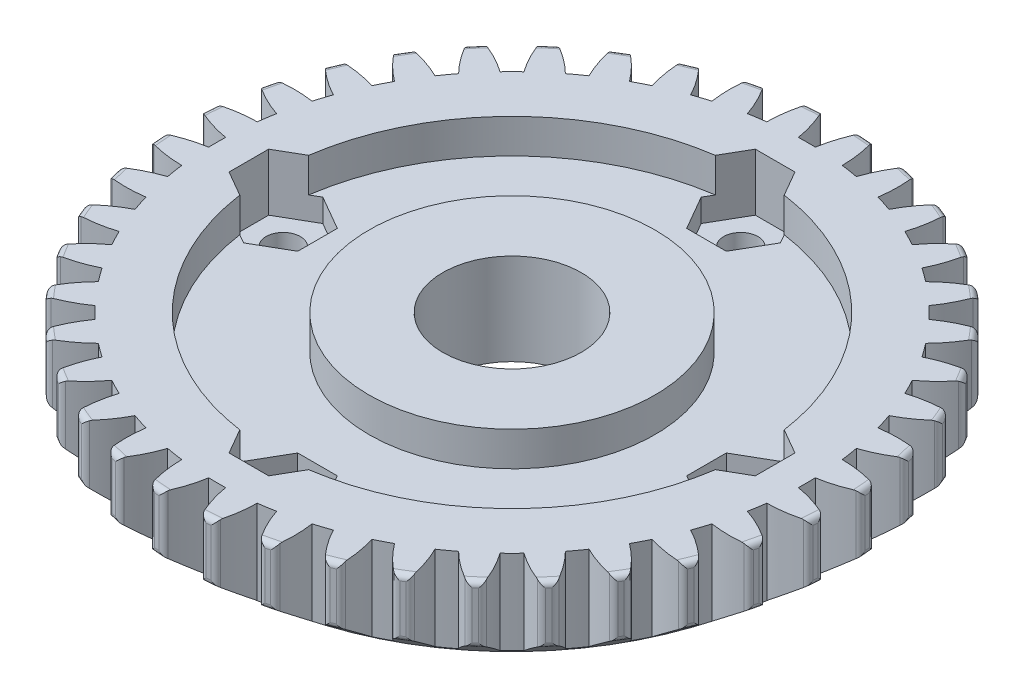
SolidWorks part; units mm, degrees
material "尼龙 101"
ref_plane "前视基准面" through (0, 0, 0) normal (0, 0, 1) x (1, 0, 0)
ref_plane "上视基准面" through (0, 0, 0) normal (0, 1, 0) x (1, 0, 0)
ref_plane "右视基准面" through (0, 0, 0) normal (1, 0, 0) x (0, 0, -1)
sketch "草图2" plane through (0, 0, 0) normal (0, 1, 0) x (1, 0, 0)
  line L0 (0, -1060.6686) -> (0, -25.7803) construction
  line L1 (0, 0) -> (39.3659, 0) construction
  line L2 (0, -12.5) -> (0, 15.5) construction
  line L3 (0, 25.7803) -> (0, 1032.0709) construction
  arc A127 (-0.7399, 25.7696) -> (-1.7209, 28.8237) centre (-11.5914, 23.9683) ccw
  arc A128 (-1.7209, 28.8237) -> (-2.8093, 28.738) centre (0, 0) ccw
  arc A129 (-2.8093, 28.738) -> (-3.3005, 25.5681) centre (7.6992, 25.4865) ccw
  arc A169 (0.7399, 25.7696) -> (-0.7399, 25.7696) centre (0, 0) ccw
  arc A170 (3.3005, 25.5681) -> (2.8093, 28.738) centre (-7.6992, 25.4865) ccw
  arc A171 (2.8093, 28.738) -> (1.7209, 28.8237) centre (0, 0) ccw
  arc A172 (1.7209, 28.8237) -> (0.7399, 25.7696) centre (11.5914, 23.9683) ccw
  arc A173 (7.2596, 24.737) -> (7.2703, 27.9447) centre (-3.6174, 26.3772) ccw
  arc A174 (7.2703, 27.9447) -> (6.2088, 28.1996) centre (0, 0) ccw
  arc A175 (6.2088, 28.1996) -> (4.762, 25.3366) centre (15.1981, 21.8599) ccw
  arc A176 (11.0399, 23.2968) -> (11.5523, 26.4634) centre (0.5534, 26.6183) ccw
  arc A177 (11.5523, 26.4634) -> (10.5437, 26.8811) centre (0, 0) ccw
  arc A178 (10.5437, 26.8811) -> (8.6669, 24.2797) centre (18.4307, 19.2133) ccw
  arc A179 (14.5485, 21.2829) -> (15.5499, 24.3304) centre (4.7106, 26.204) ccw
  arc A180 (15.5499, 24.3304) -> (14.619, 24.9008) centre (0, 0) ccw
  arc A181 (14.619, 24.9008) -> (12.3584, 22.625) centre (21.2094, 16.0936) ccw
  arc A182 (17.6987, 18.745) -> (19.1645, 21.5983) centre (8.7518, 25.1445) ccw
  arc A183 (19.1645, 21.5983) -> (18.3344, 22.3073) centre (0, 0) ccw
  arc A184 (18.3344, 22.3073) -> (15.7456, 20.4132) centre (23.4658, 12.5775) ccw
  arc A185 (20.4132, 15.7456) -> (22.3073, 18.3344) centre (12.5775, 23.4658) ccw
  arc A186 (22.3073, 18.3344) -> (21.5983, 19.1645) centre (0, 0) ccw
  arc A187 (21.5983, 19.1645) -> (18.745, 17.6987) centre (25.1445, 8.7518) ccw
  arc A188 (22.625, 12.3584) -> (24.9008, 14.619) centre (16.0936, 21.2094) ccw
  arc A189 (24.9008, 14.619) -> (24.3304, 15.5499) centre (0, 0) ccw
  arc A190 (24.3304, 15.5499) -> (21.2829, 14.5485) centre (26.204, 4.7106) ccw
  arc A191 (24.2797, 8.6669) -> (26.8811, 10.5437) centre (19.2133, 18.4307) ccw
  arc A192 (26.8811, 10.5437) -> (26.4634, 11.5523) centre (0, 0) ccw
  arc A193 (26.4634, 11.5523) -> (23.2968, 11.0399) centre (26.6183, 0.5534) ccw
  arc A194 (25.3366, 4.762) -> (28.1996, 6.2088) centre (21.8599, 15.1981) ccw
  arc A195 (28.1996, 6.2088) -> (27.9447, 7.2703) centre (0, 0) ccw
  arc A196 (27.9447, 7.2703) -> (24.737, 7.2596) centre (26.3772, -3.6174) ccw
  arc A197 (25.7696, 0.7399) -> (28.8237, 1.7209) centre (23.9683, 11.5914) ccw
  arc A198 (28.8237, 1.7209) -> (28.738, 2.8093) centre (0, 0) ccw
  arc A199 (28.738, 2.8093) -> (25.5681, 3.3005) centre (25.4865, -7.6992) ccw
  arc A200 (25.5681, -3.3005) -> (28.738, -2.8093) centre (25.4865, 7.6992) ccw
  arc A201 (28.738, -2.8093) -> (28.8237, -1.7209) centre (0, 0) ccw
  arc A202 (28.8237, -1.7209) -> (25.7696, -0.7399) centre (23.9683, -11.5914) ccw
  arc A203 (24.737, -7.2596) -> (27.9447, -7.2703) centre (26.3772, 3.6174) ccw
  arc A204 (27.9447, -7.2703) -> (28.1996, -6.2088) centre (0, 0) ccw
  arc A205 (28.1996, -6.2088) -> (25.3366, -4.762) centre (21.8599, -15.1981) ccw
  arc A206 (23.2968, -11.0399) -> (26.4634, -11.5523) centre (26.6183, -0.5534) ccw
  arc A207 (26.4634, -11.5523) -> (26.8811, -10.5437) centre (0, 0) ccw
  arc A208 (26.8811, -10.5437) -> (24.2797, -8.6669) centre (19.2133, -18.4307) ccw
  arc A209 (21.2829, -14.5485) -> (24.3304, -15.5499) centre (26.204, -4.7106) ccw
  arc A210 (24.3304, -15.5499) -> (24.9008, -14.619) centre (0, 0) ccw
  arc A211 (24.9008, -14.619) -> (22.625, -12.3584) centre (16.0936, -21.2094) ccw
  arc A212 (18.745, -17.6987) -> (21.5983, -19.1645) centre (25.1445, -8.7518) ccw
  arc A213 (21.5983, -19.1645) -> (22.3073, -18.3344) centre (0, 0) ccw
  arc A214 (22.3073, -18.3344) -> (20.4132, -15.7456) centre (12.5775, -23.4658) ccw
  arc A215 (15.7456, -20.4132) -> (18.3344, -22.3073) centre (23.4658, -12.5775) ccw
  arc A216 (18.3344, -22.3073) -> (19.1645, -21.5983) centre (0, 0) ccw
  arc A217 (19.1645, -21.5983) -> (17.6987, -18.745) centre (8.7518, -25.1445) ccw
  arc A218 (12.3584, -22.625) -> (14.619, -24.9008) centre (21.2094, -16.0936) ccw
  arc A219 (14.619, -24.9008) -> (15.5499, -24.3304) centre (0, 0) ccw
  arc A220 (15.5499, -24.3304) -> (14.5485, -21.2829) centre (4.7106, -26.204) ccw
  arc A221 (8.6669, -24.2797) -> (10.5437, -26.8811) centre (18.4307, -19.2133) ccw
  arc A222 (10.5437, -26.8811) -> (11.5523, -26.4634) centre (0, 0) ccw
  arc A223 (11.5523, -26.4634) -> (11.0399, -23.2968) centre (0.5534, -26.6183) ccw
  arc A224 (4.762, -25.3366) -> (6.2088, -28.1996) centre (15.1981, -21.8599) ccw
  arc A225 (6.2088, -28.1996) -> (7.2703, -27.9447) centre (0, 0) ccw
  arc A226 (7.2703, -27.9447) -> (7.2596, -24.737) centre (-3.6174, -26.3772) ccw
  arc A227 (0.7399, -25.7696) -> (1.7209, -28.8237) centre (11.5914, -23.9683) ccw
  arc A228 (1.7209, -28.8237) -> (2.8093, -28.738) centre (0, 0) ccw
  arc A229 (2.8093, -28.738) -> (3.3005, -25.5681) centre (-7.6992, -25.4865) ccw
  arc A230 (-3.3005, -25.5681) -> (-2.8093, -28.738) centre (7.6992, -25.4865) ccw
  arc A231 (-2.8093, -28.738) -> (-1.7209, -28.8237) centre (0, 0) ccw
  arc A232 (-1.7209, -28.8237) -> (-0.7399, -25.7696) centre (-11.5914, -23.9683) ccw
  arc A233 (-7.2596, -24.737) -> (-7.2703, -27.9447) centre (3.6174, -26.3772) ccw
  arc A234 (-7.2703, -27.9447) -> (-6.2088, -28.1996) centre (0, 0) ccw
  arc A235 (-6.2088, -28.1996) -> (-4.762, -25.3366) centre (-15.1981, -21.8599) ccw
  arc A236 (-11.0399, -23.2968) -> (-11.5523, -26.4634) centre (-0.5534, -26.6183) ccw
  arc A237 (-11.5523, -26.4634) -> (-10.5437, -26.8811) centre (0, 0) ccw
  arc A238 (-10.5437, -26.8811) -> (-8.6669, -24.2797) centre (-18.4307, -19.2133) ccw
  arc A239 (-14.5485, -21.2829) -> (-15.5499, -24.3304) centre (-4.7106, -26.204) ccw
  arc A240 (-15.5499, -24.3304) -> (-14.619, -24.9008) centre (0, 0) ccw
  arc A241 (-14.619, -24.9008) -> (-12.3584, -22.625) centre (-21.2094, -16.0936) ccw
  arc A242 (-17.6987, -18.745) -> (-19.1645, -21.5983) centre (-8.7518, -25.1445) ccw
  arc A243 (-19.1645, -21.5983) -> (-18.3344, -22.3073) centre (0, 0) ccw
  arc A244 (-18.3344, -22.3073) -> (-15.7456, -20.4132) centre (-23.4658, -12.5775) ccw
  arc A245 (-20.4132, -15.7456) -> (-22.3073, -18.3344) centre (-12.5775, -23.4658) ccw
  arc A246 (-22.3073, -18.3344) -> (-21.5983, -19.1645) centre (0, 0) ccw
  arc A247 (-21.5983, -19.1645) -> (-18.745, -17.6987) centre (-25.1445, -8.7518) ccw
  arc A248 (-22.625, -12.3584) -> (-24.9008, -14.619) centre (-16.0936, -21.2094) ccw
  arc A249 (-24.9008, -14.619) -> (-24.3304, -15.5499) centre (0, 0) ccw
  arc A250 (-24.3304, -15.5499) -> (-21.2829, -14.5485) centre (-26.204, -4.7106) ccw
  arc A251 (-24.2797, -8.6669) -> (-26.8811, -10.5437) centre (-19.2133, -18.4307) ccw
  arc A252 (-26.8811, -10.5437) -> (-26.4634, -11.5523) centre (0, 0) ccw
  arc A253 (-26.4634, -11.5523) -> (-23.2968, -11.0399) centre (-26.6183, -0.5534) ccw
  arc A254 (-25.3366, -4.762) -> (-28.1996, -6.2088) centre (-21.8599, -15.1981) ccw
  arc A255 (-28.1996, -6.2088) -> (-27.9447, -7.2703) centre (0, 0) ccw
  arc A256 (-27.9447, -7.2703) -> (-24.737, -7.2596) centre (-26.3772, 3.6174) ccw
  arc A257 (-25.7696, -0.7399) -> (-28.8237, -1.7209) centre (-23.9683, -11.5914) ccw
  arc A258 (-28.8237, -1.7209) -> (-28.738, -2.8093) centre (0, 0) ccw
  arc A259 (-28.738, -2.8093) -> (-25.5681, -3.3005) centre (-25.4865, 7.6992) ccw
  arc A260 (-25.5681, 3.3005) -> (-28.738, 2.8093) centre (-25.4865, -7.6992) ccw
  arc A261 (-28.738, 2.8093) -> (-28.8237, 1.7209) centre (0, 0) ccw
  arc A262 (-28.8237, 1.7209) -> (-25.7696, 0.7399) centre (-23.9683, 11.5914) ccw
  arc A263 (-24.737, 7.2596) -> (-27.9447, 7.2703) centre (-26.3772, -3.6174) ccw
  arc A264 (-27.9447, 7.2703) -> (-28.1996, 6.2088) centre (0, 0) ccw
  arc A265 (-28.1996, 6.2088) -> (-25.3366, 4.762) centre (-21.8599, 15.1981) ccw
  arc A266 (-23.2968, 11.0399) -> (-26.4634, 11.5523) centre (-26.6183, 0.5534) ccw
  arc A267 (-26.4634, 11.5523) -> (-26.8811, 10.5437) centre (0, 0) ccw
  arc A268 (-26.8811, 10.5437) -> (-24.2797, 8.6669) centre (-19.2133, 18.4307) ccw
  arc A269 (-21.2829, 14.5485) -> (-24.3304, 15.5499) centre (-26.204, 4.7106) ccw
  arc A270 (-24.3304, 15.5499) -> (-24.9008, 14.619) centre (0, 0) ccw
  arc A271 (-24.9008, 14.619) -> (-22.625, 12.3584) centre (-16.0936, 21.2094) ccw
  arc A272 (-18.745, 17.6987) -> (-21.5983, 19.1645) centre (-25.1445, 8.7518) ccw
  arc A273 (-21.5983, 19.1645) -> (-22.3073, 18.3344) centre (0, 0) ccw
  arc A274 (-22.3073, 18.3344) -> (-20.4132, 15.7456) centre (-12.5775, 23.4658) ccw
  arc A275 (-15.7456, 20.4132) -> (-18.3344, 22.3073) centre (-23.4658, 12.5775) ccw
  arc A276 (-18.3344, 22.3073) -> (-19.1645, 21.5983) centre (0, 0) ccw
  arc A277 (-19.1645, 21.5983) -> (-17.6987, 18.745) centre (-8.7518, 25.1445) ccw
  arc A278 (-12.3584, 22.625) -> (-14.619, 24.9008) centre (-21.2094, 16.0936) ccw
  arc A279 (-14.619, 24.9008) -> (-15.5499, 24.3304) centre (0, 0) ccw
  arc A280 (-15.5499, 24.3304) -> (-14.5485, 21.2829) centre (-4.7106, 26.204) ccw
  arc A281 (-8.6669, 24.2797) -> (-10.5437, 26.8811) centre (-18.4307, 19.2133) ccw
  arc A282 (-10.5437, 26.8811) -> (-11.5523, 26.4634) centre (0, 0) ccw
  arc A283 (-11.5523, 26.4634) -> (-11.0399, 23.2968) centre (-0.5534, 26.6183) ccw
  arc A284 (-4.762, 25.3366) -> (-6.2088, 28.1996) centre (-15.1981, 21.8599) ccw
  arc A285 (-6.2088, 28.1996) -> (-7.2703, 27.9447) centre (0, 0) ccw
  arc A286 (-7.2703, 27.9447) -> (-7.2596, 24.737) centre (3.6174, 26.3772) ccw
  circle A288 centre (0, -20) radius 1.5
  arc A322 (4.762, 25.3366) -> (3.3005, 25.5681) centre (0, 0) ccw
  arc A323 (8.6669, 24.2797) -> (7.2596, 24.737) centre (0, 0) ccw
  arc A324 (12.3584, 22.625) -> (11.0399, 23.2968) centre (0, 0) ccw
  arc A325 (15.7456, 20.4132) -> (14.5485, 21.2829) centre (0, 0) ccw
  arc A326 (18.745, 17.6987) -> (17.6987, 18.745) centre (0, 0) ccw
  arc A327 (21.2829, 14.5485) -> (20.4132, 15.7456) centre (0, 0) ccw
  arc A328 (23.2968, 11.0399) -> (22.625, 12.3584) centre (0, 0) ccw
  arc A329 (24.737, 7.2596) -> (24.2797, 8.6669) centre (0, 0) ccw
  arc A330 (25.5681, 3.3005) -> (25.3366, 4.762) centre (0, 0) ccw
  arc A331 (25.7696, -0.7399) -> (25.7696, 0.7399) centre (0, 0) ccw
  arc A332 (25.3366, -4.762) -> (25.5681, -3.3005) centre (0, 0) ccw
  arc A333 (24.2797, -8.6669) -> (24.737, -7.2596) centre (0, 0) ccw
  arc A334 (22.625, -12.3584) -> (23.2968, -11.0399) centre (0, 0) ccw
  arc A335 (20.4132, -15.7456) -> (21.2829, -14.5485) centre (0, 0) ccw
  arc A336 (17.6987, -18.745) -> (18.745, -17.6987) centre (0, 0) ccw
  arc A337 (14.5485, -21.2829) -> (15.7456, -20.4132) centre (0, 0) ccw
  arc A338 (11.0399, -23.2968) -> (12.3584, -22.625) centre (0, 0) ccw
  arc A339 (7.2596, -24.737) -> (8.6669, -24.2797) centre (0, 0) ccw
  arc A340 (3.3005, -25.5681) -> (4.762, -25.3366) centre (0, 0) ccw
  arc A341 (-4.762, -25.3366) -> (-3.3005, -25.5681) centre (0, 0) ccw
  arc A342 (-8.6669, -24.2797) -> (-7.2596, -24.737) centre (0, 0) ccw
  arc A343 (-12.3584, -22.625) -> (-11.0399, -23.2968) centre (0, 0) ccw
  arc A344 (-15.7456, -20.4132) -> (-14.5485, -21.2829) centre (0, 0) ccw
  arc A345 (-18.745, -17.6987) -> (-17.6987, -18.745) centre (0, 0) ccw
  arc A346 (-21.2829, -14.5485) -> (-20.4132, -15.7456) centre (0, 0) ccw
  arc A347 (-23.2968, -11.0399) -> (-22.625, -12.3584) centre (0, 0) ccw
  arc A348 (-24.737, -7.2596) -> (-24.2797, -8.6669) centre (0, 0) ccw
  arc A349 (-25.5681, -3.3005) -> (-25.3366, -4.762) centre (0, 0) ccw
  arc A350 (-25.3366, 4.762) -> (-25.5681, 3.3005) centre (0, 0) ccw
  arc A351 (-24.2797, 8.6669) -> (-24.737, 7.2596) centre (0, 0) ccw
  arc A352 (-22.625, 12.3584) -> (-23.2968, 11.0399) centre (0, 0) ccw
  arc A353 (-20.4132, 15.7456) -> (-21.2829, 14.5485) centre (0, 0) ccw
  arc A354 (-17.6987, 18.745) -> (-18.745, 17.6987) centre (0, 0) ccw
  arc A355 (-14.5485, 21.2829) -> (-15.7456, 20.4132) centre (0, 0) ccw
  arc A356 (-11.0399, 23.2968) -> (-12.3584, 22.625) centre (0, 0) ccw
  arc A357 (-7.2596, 24.737) -> (-8.6669, 24.2797) centre (0, 0) ccw
  arc A358 (-3.3005, 25.5681) -> (-4.762, 25.3366) centre (0, 0) ccw
  circle A360 centre (0, 0) radius 6.05
  circle A361 centre (-20, 0) radius 1.5
  circle A362 centre (0, 20) radius 1.5
  circle A363 centre (20, 0) radius 1.5
  arc A364 (-25.7696, 0.7399) -> (-25.7696, -0.7399) centre (0, 0) ccw
  arc A365 (-0.7399, -25.7696) -> (0.7399, -25.7696) centre (0, 0) ccw
  point P241 (0, 0)
  point P294 (0, 0)
  point P302 (0, 1.5)
  point P308 (0, 0)
  dimension "D1" = 51.5605
  dimension "D4" = 26.6241
  dimension "D5" = 28.875
  dimension "D6" = 11
  dimension "D7" = 11
  dimension "D9" = 3
  dimension "D11" = 4
  dimension "D17" = 12.1
  dimension "D2" = 25.7696
  dimension "D3" = 26.6241
  dimension "D8" = 25.5681
  dimension "D10" = 20
extrude "凸台-拉伸2" add sketch "草图2" along normal blind 8 contours A129 A358 A284 A285 A286 A357 A281 A282 A283 A356 A278 A279 A280 A355 A275 A276 A277 A354 A272 A273 A274 A353 A269 A270 A271 A352 A266 A267 A268 A351 A263 A264 A265 A350 A257 A258 A259 A349 A254 A255 A256 A348 A251 A252 A253 A347 A248 A249 A250 region at (0, 0, -24.965)
sketch "草图3" plane through (0, 8, 0) normal (0, 1, 0) x (1, 0, 0)
  line L0 (-17, -1.7321) -> (-17, 1.7321)
  line L1 (1.7321, -17) -> (-1.7321, -17)
  line L2 (-1.7321, -17) -> (-3.4641, -20)
  line L3 (-3.4641, -20) -> (-1.7321, -23)
  line L4 (-1.7321, -23) -> (1.7321, -23)
  line L5 (1.7321, -23) -> (3.4641, -20)
  line L6 (3.4641, -20) -> (1.7321, -17)
  line L7 (-17, 1.7321) -> (-20, 3.4641)
  line L8 (-20, 3.4641) -> (-23, 1.7321)
  line L9 (-23, 1.7321) -> (-23, -1.7321)
  line L10 (-23, -1.7321) -> (-20, -3.4641)
  line L11 (-20, -3.4641) -> (-17, -1.7321)
  line L12 (-1.7321, 17) -> (1.7321, 17)
  line L13 (1.7321, 17) -> (3.4641, 20)
  line L14 (3.4641, 20) -> (1.7321, 23)
  line L15 (1.7321, 23) -> (-1.7321, 23)
  line L16 (-1.7321, 23) -> (-3.4641, 20)
  line L17 (-3.4641, 20) -> (-1.7321, 17)
  line L18 (17, 1.7321) -> (17, -1.7321)
  line L19 (17, -1.7321) -> (20, -3.4641)
  line L20 (20, -3.4641) -> (23, -1.7321)
  line L21 (23, -1.7321) -> (23, 1.7321)
  line L22 (23, 1.7321) -> (20, 3.4641)
  line L23 (20, 3.4641) -> (17, 1.7321)
  line L24 (0, 0) -> (0, -11.9745) construction
  circle A2 centre (0, 0) radius 12.5
  circle A3 centre (0, 0) radius 21
  circle A12 centre (0, -20) radius 3 construction
  point P37 (0, 0)
  dimension "D1" = 25
  dimension "D2" = 42
  dimension "D3" = 6
  dimension "D4" = 20
extrude "切除-拉伸1" cut sketch "草图3" against normal blind 3 contours L5 A3 L20 L19 L18 L23 L22 L14 L13 L12 L17 L16 L8 L7 L0 L11 L10 L3 L2 L1 L6 A2 | L3 A3 L5 L6 L1 L2 | A3 L3 L4 L5 | L8 A3 L10 L11 L0 L7 | A3 L8 L9 L10 | A3 L20 L21 L22 | L20 A3 L22 L23 L18 L19 | A3 L14 L15 L16 | L14 A3 L16 L17 L12 L13 region at (-19.16, 8, 0) region at (-16.4122, 8, 0) region at (-21.8752, 8, 0) region at (0, 8, 21.8752) region at (0, 8, 19.16) region at (0, 8, -19.16) region at (0, 8, -21.8752) region at (21.8752, 8, 0) region at (19.16, 8, 0)
sketch "草图4" plane through (0, 5, 0) normal (0, 1, 0) x (1, 0, 0)
  line L2 (-3.0121, -20.7829) -> (-1.7321, -23) construction
  line L3 (-1.7321, -23) -> (1.7321, -23) construction
  line L4 (1.7321, -23) -> (3.0121, -20.7829) construction
  line L6 (-23, -1.7321) -> (-20, -3.4641)
  line L7 (-3.0121, -20.7829) -> (-1.7321, -23)
  line L8 (-1.7321, -23) -> (1.7321, -23)
  line L9 (1.7321, -23) -> (3.0121, -20.7829)
  line L10 (-20, -3.4641) -> (-17, -1.7321)
  line L11 (1.7321, -23) -> (3.4641, -20)
  line L12 (3.4641, -20) -> (1.7321, -17)
  line L13 (1.7321, -17) -> (-1.7321, -17)
  line L14 (-1.7321, -17) -> (-3.4641, -20)
  line L15 (-3.4641, -20) -> (-1.7321, -23)
  line L16 (-1.7321, -23) -> (1.7321, -23)
  line L17 (-17, -1.7321) -> (-17, 1.7321)
  line L18 (-17, 1.7321) -> (-20, 3.4641)
  line L19 (-20, 3.4641) -> (-23, 1.7321)
  line L20 (-23, 1.7321) -> (-23, -1.7321)
  line L21 (-1.7321, 23) -> (-3.4641, 20)
  line L22 (-3.4641, 20) -> (-1.7321, 17)
  line L23 (-1.7321, 17) -> (1.7321, 17)
  line L24 (1.7321, 17) -> (3.4641, 20)
  line L25 (3.4641, 20) -> (1.7321, 23)
  line L26 (1.7321, 23) -> (-1.7321, 23)
  line L27 (23, 1.7321) -> (20, 3.4641)
  line L28 (20, 3.4641) -> (17, 1.7321)
  line L29 (17, 1.7321) -> (17, -1.7321)
  line L30 (17, -1.7321) -> (20, -3.4641)
  line L31 (20, -3.4641) -> (23, -1.7321)
  line L32 (23, -1.7321) -> (23, 1.7321)
  circle A0 centre (0, -20) radius 1.5 construction
  circle A1 centre (0, -20) radius 1.5
  circle A2 centre (0, -20) radius 3 construction
  point P35 (0, 0)
  circle M9 centre (20, 0) radius 1.5
  circle M11 centre (-20, 0) radius 1.5
  circle M12 centre (0, -20) radius 1.5
  line M14 (20.7829, -3.0121) -> (23, -1.7321)
  line M15 (23, -1.7321) -> (23, 1.7321)
  line M16 (23, 1.7321) -> (20.7829, 3.0121)
  line M22 (-20.7829, 3.0121) -> (-23, 1.7321)
  line M23 (-23, 1.7321) -> (-23, -1.7321)
  line M24 (-23, -1.7321) -> (-20.7829, -3.0121)
  line M26 (-3.0121, -20.7829) -> (-1.7321, -23)
  line M27 (-1.7321, -23) -> (1.7321, -23)
  line M28 (1.7321, -23) -> (3.0121, -20.7829)
extrude "切除-拉伸2" cut sketch "草图4" against normal blind 2 contours L18 L19 L6 L10 L17 M22 M23 M24 M11 | L30 L31 L27 L28 L29 M14 M15 M16 M9 | L14 L15 L11 L12 L13 M26 M27 M28 M12 | L25 L26 L21 L22 L23 L24 region at (-22.9083, 5, 0) region at (-3.1587, 5, 20.3456) region at (22.9083, 5, 0)
sketch3d "3D草图1"
  line L0 (0, 0, 0) -> (0, -45.0639, 0) construction
sketch "草图6" plane through (0, 0, 0) normal (1, 0, 0) x (0, 0, -1)
  line L0 (-30, 4) -> (-30, 0)
  line L1 (-30, 4) -> (-25, 0)
  line L2 (-25, 0) -> (-30, 0)
  line L3 (0, 0) -> (7.7923, 0) construction
  line L4 (0, 200000) -> (0, -200045.0639) construction
  point P2 (0, 0)
  dimension "D2" = 4
  dimension "D3" = 25
  dimension "D4" = 5
revolve "切除-旋转2" cut sketch "草图6" angle 360 about L0
fillet "圆角1" radius 0.5 160 edges at (-6.7407, 8, 28.0772) (-6.2088, 5.55, 28.1996) (-6.7407, 3.1, 28.0772) (-7.2703, 5.55, 27.9447) (-11.05, 8, 26.677) (-10.5437, 5.55, 26.8811) (-11.05, 3.1, 26.677) (-11.5523, 5.55, 26.4634) (-15.0871, 8, 24.62) (-14.619, 5.55, 24.9008) (-15.0871, 3.1, 24.62) (-15.5499, 5.55, 24.3304) (-18.7528, 8, 21.9567) (-18.3344, 5.55, 22.3073) (-18.7528, 3.1, 21.9567) (-19.1645, 5.55, 21.5983) (-21.9567, 8, 18.7528) (-21.5983, 5.55, 19.1645) (-21.9567, 3.1, 18.7528) (-22.3073, 5.55, 18.3344) (-24.62, 8, 15.0871) (-24.3304, 5.55, 15.5499) (-24.62, 3.1, 15.0871) (-24.9008, 5.55, 14.619) (-26.677, 8, 11.05) (-26.4634, 5.55, 11.5523) (-26.677, 3.1, 11.05) (-26.8811, 5.55, 10.5437) (-28.0772, 8, 6.7407) (-27.9447, 5.55, 7.2703) (-28.0772, 3.1, 6.7407) (-28.1996, 5.55, 6.2088) (-28.786, 8, 2.2655) (-28.738, 5.55, 2.8093) (-28.786, 3.1, 2.2655) (-28.8237, 5.55, 1.7209) (-28.786, 8, -2.2655) (-28.8237, 5.55, -1.7209) (-28.786, 3.1, -2.2655) (-28.738, 5.55, -2.8093) (-28.0772, 8, -6.7407) (-28.1996, 5.55, -6.2088) (-28.0772, 3.1, -6.7407) (-27.9447, 5.55, -7.2703) (-26.677, 8, -11.05) (-26.8811, 5.55, -10.5437) (-26.677, 3.1, -11.05) (-26.4634, 5.55, -11.5523) (-24.62, 8, -15.0871) (-24.9008, 5.55, -14.619) (-24.62, 3.1, -15.0871) (-24.3304, 5.55, -15.5499) (-21.9567, 8, -18.7528) (-22.3073, 5.55, -18.3344) (-21.9567, 3.1, -18.7528) (-21.5983, 5.55, -19.1645) (-18.7528, 8, -21.9567) (-19.1645, 5.55, -21.5983) (-18.7528, 3.1, -21.9567) (-18.3344, 5.55, -22.3073) (-15.0871, 8, -24.62) (-15.5499, 5.55, -24.3304) (-15.0871, 3.1, -24.62) (-14.619, 5.55, -24.9008) (-11.05, 8, -26.677) (-11.5523, 5.55, -26.4634) (-11.05, 3.1, -26.677) (-10.5437, 5.55, -26.8811) (-6.7407, 8, -28.0772) (-7.2703, 5.55, -27.9447) (-6.7407, 3.1, -28.0772) (-6.2088, 5.55, -28.1996) (-2.2655, 8, -28.786) (-2.8093, 5.55, -28.738) (-2.2655, 3.1, -28.786) (-1.7209, 5.55, -28.8237) (2.2655, 8, -28.786) (1.7209, 5.55, -28.8237) (2.2655, 3.1, -28.786) (2.8093, 5.55, -28.738) (6.7407, 8, -28.0772) (6.2088, 5.55, -28.1996) (6.7407, 3.1, -28.0772) (7.2703, 5.55, -27.9447) (11.05, 8, -26.677) (10.5437, 5.55, -26.8811) (11.05, 3.1, -26.677) (11.5523, 5.55, -26.4634) (15.0871, 8, -24.62) (14.619, 5.55, -24.9008) (15.0871, 3.1, -24.62) (15.5499, 5.55, -24.3304) (18.7528, 8, -21.9567) (18.3344, 5.55, -22.3073) (18.7528, 3.1, -21.9567) (19.1645, 5.55, -21.5983) (21.9567, 8, -18.7528) (21.5983, 5.55, -19.1645) (21.9567, 3.1, -18.7528) (22.3073, 5.55, -18.3344) (24.62, 8, -15.0871) (24.3304, 5.55, -15.5499) (24.62, 3.1, -15.0871) (24.9008, 5.55, -14.619) (26.677, 8, -11.05) (26.4634, 5.55, -11.5523) (26.677, 3.1, -11.05) (26.8811, 5.55, -10.5437) (28.0772, 8, -6.7407) (27.9447, 5.55, -7.2703) (28.0772, 3.1, -6.7407) (28.1996, 5.55, -6.2088) (28.786, 8, -2.2655) (28.738, 5.55, -2.8093) (28.786, 3.1, -2.2655) (28.8237, 5.55, -1.7209) (28.786, 8, 2.2655) (28.8237, 5.55, 1.7209) (28.786, 3.1, 2.2655) (28.738, 5.55, 2.8093) (28.0772, 8, 6.7407) (28.1996, 5.55, 6.2088) (28.0772, 3.1, 6.7407) (27.9447, 5.55, 7.2703) (26.677, 8, 11.05) (26.8811, 5.55, 10.5437) (26.677, 3.1, 11.05) (26.4634, 5.55, 11.5523) (-2.2655, 8, 28.786) (-1.7209, 5.55, 28.8237) (-2.2655, 3.1, 28.786) (-2.8093, 5.55, 28.738) (2.2655, 8, 28.786) (2.8093, 5.55, 28.738) (2.2655, 3.1, 28.786) (1.7209, 5.55, 28.8237) (6.7407, 8, 28.0772) (7.2703, 5.55, 27.9447) (6.7407, 3.1, 28.0772) (6.2088, 5.55, 28.1996) (11.05, 8, 26.677) (11.5523, 5.55, 26.4634) (11.05, 3.1, 26.677) (10.5437, 5.55, 26.8811) (15.0871, 8, 24.62) (15.5499, 5.55, 24.3304) (15.0871, 3.1, 24.62) (14.619, 5.55, 24.9008) (18.7528, 8, 21.9567) (19.1645, 5.55, 21.5983) (18.7528, 3.1, 21.9567) (18.3344, 5.55, 22.3073) (21.9567, 8, 18.7528) (22.3073, 5.55, 18.3344) (21.9567, 3.1, 18.7528) (21.5983, 5.55, 19.1645) (24.62, 8, 15.0871) (24.9008, 5.55, 14.619) (24.62, 3.1, 15.0871) (24.3304, 5.55, 15.5499)
